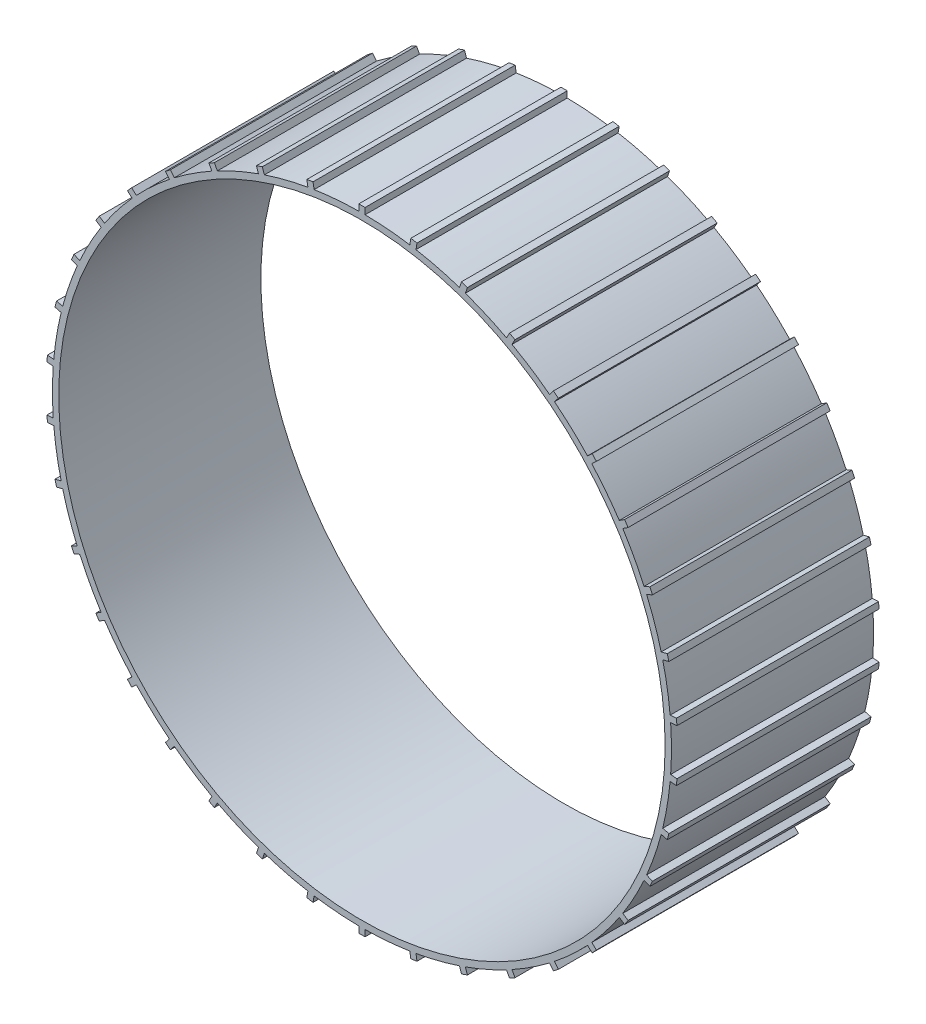
SolidWorks part; units mm, degrees
material "Rubber"
ref_plane "Front Plane" through (0, 0, 0) normal (0, 0, 1) x (1, 0, 0)
ref_plane "Top Plane" through (0, 0, 0) normal (0, 1, 0) x (1, 0, 0)
ref_plane "Right Plane" through (0, 0, 0) normal (1, 0, 0) x (0, 0, -1)
sketch "Sketch1" plane through (0, 0, 0) normal (0, 0, 1) x (1, 0, 0)
  circle A0 centre (0, 0) radius 155.575
  circle A1 centre (0, 0) radius 152.4
  dimension "D1" = 304.8
  dimension "D2" = 311.15
extrude "Boss-Extrude1" add sketch "Sketch1" along normal blind 101.6
sketch "Sketch2" plane through (0, 0, 101.6) normal (0, 0, 1) x (1, 0, 0)
  line L0 (-1.5748, 155.567) -> (-1.5748, 158.75)
  line L1 (-1.5748, 158.75) -> (1.5748, 158.75)
  line L2 (1.5748, 158.75) -> (1.5748, 155.567)
  circle A0 centre (0, 0) radius 155.575 construction
  circle A2 centre (0, 0) radius 155.575
  arc A3 (-1.5748, 155.567) -> (1.5748, 155.567) centre (0, 0) ccw
  circle M1 centre (0, 0) radius 155.575
  dimension "D1" = 1.5748
  dimension "D2" = 1.5748
  dimension "D3" = 158.75
  dimension "D4" = 0
extrude "Boss-Extrude2" add sketch "Sketch2" against normal through all contours L2 L1 L0 M1 region at (0, 157.1612, 101.6)
pattern_circular "CirPattern1" count 38 over 360 about axis through (0, 0, 101.6) along (0, 0, 1) of "Boss-Extrude2"
